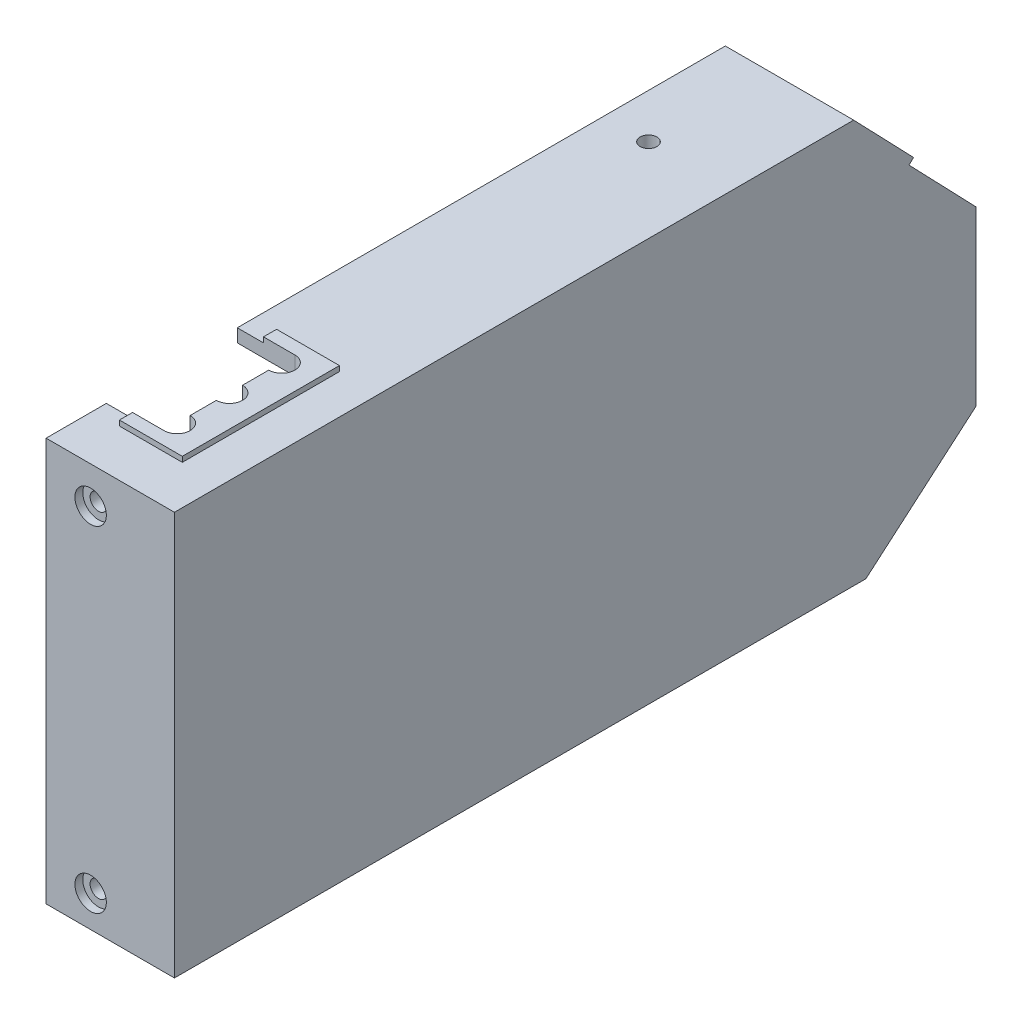
SolidWorks part; units mm, degrees
ref_plane "Front Plane" through (0, 0, 0) normal (0, 0, 1) x (1, 0, 0)
ref_plane "Top Plane" through (0, 0, 0) normal (0, 1, 0) x (1, 0, 0)
ref_plane "Right Plane" through (0, 0, 0) normal (1, 0, 0) x (0, 0, -1)
sketch "Sketch1" plane through (0, 0, 0) normal (1, 0, 0) x (0, 0, -1)
  line L0 (0, 0) -> (0, 77)
  line L1 (0, 77) -> (128, 77)
  line L2 (128, 77) -> (153, 51)
  line L3 (153, 51) -> (153, 18)
  line L4 (153, 18) -> (132, 0)
  line L5 (132, 0) -> (0, 0)
  dimension "D1" = 132
  dimension "D2" = 77
  dimension "D3" = 128
  dimension "D4" = 26
  dimension "D5" = 153
  dimension "D6" = 18
extrude "Base" add sketch "Sketch1" along normal blind 2.5
sketch "Sketch11" plane through (0, 0, 0) normal (-1, 0, 0) x (0, 0, 1)
  line L12 (-131.0752, 2.5) -> (-2.5, 2.5)
  line L13 (-2.5, 2.5) -> (-2.5, 74.5)
  line L14 (-2.5, 74.5) -> (-126.9356, 74.5)
  line L15 (-126.9356, 74.5) -> (-150.5, 49.9931)
  line L16 (-150.5, 49.9931) -> (-150.5, 19.1498)
  line L17 (-150.5, 19.1498) -> (-131.0752, 2.5)
  line L18 (-131.0752, 2.5) -> (-2.5, 2.5)
  line L19 (-2.5, 2.5) -> (-2.5, 74.5)
  line L20 (-2.5, 74.5) -> (-126.9356, 74.5)
  line L21 (-126.9356, 74.5) -> (-150.5, 49.9931)
  line L22 (-150.5, 49.9931) -> (-150.5, 19.1498)
  line L23 (-150.5, 19.1498) -> (-131.0752, 2.5)
  line M7 (-132, 0) -> (0, 0)
  line M8 (0, 0) -> (0, 77)
  line M9 (0, 77) -> (-128, 77)
  line M10 (-128, 77) -> (-153, 51)
  line M11 (-153, 51) -> (-153, 18)
  line M12 (-153, 18) -> (-132, 0)
  dimension "D1" = 2.5
extrude "Boss-Extrude6" add sketch "Sketch11" along normal blind 22 contours L23 L22 L21 L20 L19 L18 M12 M7 M8 M9 M10 M11 region at (0, 10.3005, -141.3853)
ref_plane "Middle" through (-11, 0, 0) normal (1, 0, 0) x (0, 0, -1)
ref_plane "Plane1" through (-13.5, 0, 0) normal (-1, 0, 0) x (0, 0, 1)
sketch "Sketch14" plane through (0, 0, 0) normal (0, 0, 1) x (1, 0, 0)
  line L1 (-22, 0) -> (-22, 77) construction
  line L2 (-22, 74.5) -> (-10.5, 74.5)
  line L3 (-22, 74.5) -> (-22, 66.5)
  line L4 (-22, 66.5) -> (-10.5, 66.5)
  line L5 (-10.5, 74.5) -> (-10.5, 66.5)
  line L6 (-22, 2.5) -> (-10.5, 2.5)
  line L7 (-22, 2.5) -> (-22, 10.5)
  line L8 (-22, 10.5) -> (-10.5, 10.5)
  line L9 (-10.5, 2.5) -> (-10.5, 10.5)
  line L11 (-13.5, 42.35) -> (-13.5, -42.35) construction
  point P4 (0, 0)
  point P16 (0, 0)
  dimension "D5" = 8
  dimension "D1" = 8
  dimension "D3" = 3
extrude "Boss-Extrude7" add sketch "Sketch14" against normal blind 5
sketch "Sketch15" plane through (0, 0, 0) normal (0, 0, 1) x (1, 0, 0)
  line L0 (-13.5, 42.35) -> (-13.5, -42.35) construction
  circle A0 centre (-13.5, 70) radius 3
  circle A1 centre (-13.5, 6) radius 3
  point P9 (0, 0)
  dimension "D1" = 6
  dimension "D2" = 70
  dimension "D3" = 6
extrude "Cut-Extrude3" cut sketch "Sketch15" against normal blind 1.5
sketch "Sketch16" plane through (0, 0, -1.5) normal (0, 0, 1) x (1, 0, 0)
  circle A0 centre (-13.5, 70) radius 1.6
  circle A1 centre (-13.5, 6) radius 1.6
  dimension "D1" = 3.2
extrude "Cut-Extrude4" cut sketch "Sketch16" against normal up to next
sketch "Sketch12" plane through (0, 0, 0) normal (0, -1, 0) x (1, 0, 0)
  line L2 (-13.5, 42.35) -> (-13.5, -42.35) construction
  circle A1 centre (-13.5, -106.5) radius 1.6
  point P0 (0, 0)
  point P8 (0, 0)
  dimension "D3" = 3.2
  dimension "D1" = 106.5
extrude "Cut-Extrude1" cut sketch "Sketch12" against normal through all
sketch "Sketch17" plane through (0, 77, 0) normal (0, 1, 0) x (1, 0, 0)
  line L5 (-11, -42.9) -> (-11, 42.9) construction
  line L6 (-5, 39) -> (-17, 39)
  line L7 (-5, 39) -> (-5, 9)
  line L8 (-5, 9) -> (-17, 9)
  line L9 (-17, 39) -> (-17, 9)
  line L10 (-5, 39) -> (-17, 9) construction
  line L11 (-5, 9) -> (-17, 39) construction
  line L12 (2.5, 0) -> (-22, 0) construction
  point P0 (-11, 24)
  point P5 (0, 0)
  dimension "D1" = 12
  dimension "D2" = 30
  dimension "D3" = 24
extrude "Boss-Extrude8" add sketch "Sketch17" along normal blind 1
sketch "Sketch13" plane through (0, 78, 0) normal (0, 1, 0) x (1, 0, 0)
  line L0 (-22, 11.5) -> (-11, 11.5)
  line L1 (-22, 0) -> (-22, 128) construction
  line L2 (-11, 16.5) -> (-11, 21.5)
  line L3 (-11, 26.5) -> (-11, 31.5)
  line L4 (-11, 36.5) -> (-22, 36.5)
  line L5 (-22, 36.5) -> (-22, 11.5)
  line L6 (-5, 9) -> (-5, 39) construction
  line L7 (-11, -42.9) -> (-11, 42.9) construction
  arc A0 (-11, 11.5) -> (-11, 16.5) centre (-11, 14) ccw
  arc A1 (-11, 21.5) -> (-11, 26.5) centre (-11, 24) ccw
  arc A2 (-11, 31.5) -> (-11, 36.5) centre (-11, 34) ccw
  point P9 (-5, 24)
  point P17 (0, 0)
  point P20 (0, 0)
  dimension "D1" = 5
  dimension "D4" = 10
  dimension "D5" = 10
extrude "Cut-Extrude2" cut sketch "Sketch13" against normal up to next
sketch "Sketch19" plane through (2.5, 0, 0) normal (1, 0, 0) x (0, 0, -1)
  line L0 (128, 77) -> (129.6647, 77)
  line L1 (129.6647, 77) -> (141.101, 65.1063)
  line L2 (141.101, 65.1063) -> (140.236, 64.2745)
  line L3 (153, 51) -> (128, 77) construction
  line L4 (140.236, 64.2745) -> (128, 77)
  dimension "D1" = 1.2
  dimension "D2" = 16.5
extrude "Boss-Extrude9" add sketch "Sketch19" against normal up to vertex (24.5 mm away) up to point (-22, 77, -128)
sketch "Sketch20" plane through (0, 101.7733, -105.8442) normal (0, 0.6931, -0.7208) x (-1, 0, 0)
  line L1 (11, 42.9) -> (11, -42.9) construction
  line L2 (2.5, -50.8676) -> (19.5, -50.8676)
  line L3 (2.5, -50.8676) -> (2.5, -42.3676)
  line L4 (2.5, -42.3676) -> (19.5, -42.3676)
  line L5 (19.5, -50.8676) -> (19.5, -42.3676)
  line L6 (2.5, -50.8676) -> (19.5, -42.3676) construction
  line L7 (2.5, -42.3676) -> (19.5, -50.8676) construction
  line L8 (-2.5, -50.8676) -> (-2.5, -34.3676) construction
  line L9 (22, -34.3676) -> (-2.5, -34.3676) construction
  line L10 (22, -50.8676) -> (-2.5, -50.8676) construction
  point P0 (19.6884, -37.3387)
  point P2 (11, -46.6176)
  dimension "D1" = 5
  dimension "D2" = 8
extrude "Cut-Extrude5" cut sketch "Sketch20" against normal up to vertex (1.2 mm away) up to point (2.5, 64.2745, -140.236)
sketch "Sketch21" plane through (0, 100.9416, -104.9792) normal (0, 0.6931, -0.7208) x (-1, 0, 0)
  line L0 (11, 42.9) -> (11, -42.9) construction
  line L1 (19.5, -42.3676) -> (2.5, -42.3676) construction
  line L2 (11, -45.8676) -> (22, -45.8676)
  line L3 (22, -45.8676) -> (22, -50.8676)
  line L4 (22, -50.8676) -> (22, -69.2831) construction
  line L5 (11, -50.8676) -> (22, -50.8676)
  line L6 (22, 45.7313) -> (22, 47.5334) construction
  arc A0 (11, -45.8676) -> (11, -50.8676) centre (11, -48.3676) ccw
  point P1 (0, 0)
  dimension "D1" = 5
  dimension "D2" = 6
extrude "Cut-Extrude6" cut sketch "Sketch21" against normal mid plane 10
equation "\"D5@Sketch13\"=\"D4@Sketch13\""
equation "\"D1@Sketch14\"=\"D5@Sketch14\""
